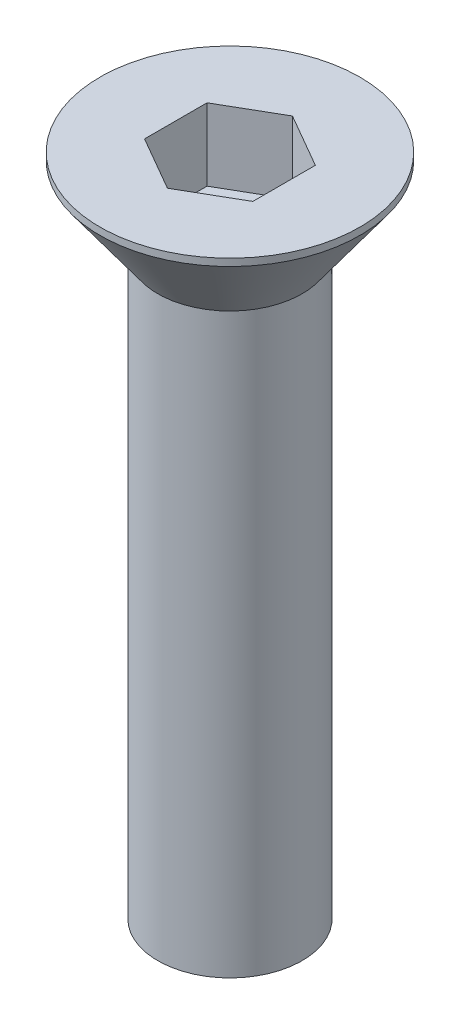
SolidWorks part; units mm, degrees
ref_plane "前视基准面" through (0, 0, 0) normal (0, 0, 1) x (1, 0, 0)
ref_plane "上视基准面" through (0, 0, 0) normal (0, 1, 0) x (1, 0, 0)
ref_plane "右视基准面" through (0, 0, 0) normal (1, 0, 0) x (0, 0, -1)
sketch "草图1" plane through (0, 0, 0) normal (0, 0, 1) x (1, 0, 0)
  line L0 (-4.4256, 0) -> (0, 0) construction
  line L1 (0, 0) -> (0, 2.2273) construction
  line L2 (0, 0) -> (1.8, 0)
  line L3 (1.8, 0) -> (1.8, -0.1)
  line L4 (1.8, -0.1) -> (1, -1.2)
  line L5 (1, -1.2) -> (0, -1.2)
  line L6 (0, -1.2) -> (0, 0)
  dimension "D1" = 1.2
  dimension "D2" = 1.8
  dimension "D3" = 0.1
  dimension "D4" = 1
revolve "旋转1" add sketch "草图1" angle 360 about L1 region at (0.738, -0.5403, 0)
sketch "草图2" plane through (0, 0, 0) normal (0, 1, 0) x (1, 0, 0)
  line L1 (0, -0.866) -> (0.75, -0.433)
  line L2 (0.75, -0.433) -> (0.75, 0.433)
  line L3 (0.75, 0.433) -> (0, 0.866)
  line L4 (0, 0.866) -> (-0.75, 0.433)
  line L5 (-0.75, 0.433) -> (-0.75, -0.433)
  line L6 (-0.75, -0.433) -> (0, -0.866)
  circle A0 centre (0, 0) radius 0.75 construction
  dimension "D1" = 1.5
extrude "切除-拉伸1" cut sketch "草图2" against normal blind 1
sketch "草图3" plane through (0, -1.2, 0) normal (0, -1, 0) x (1, 0, 0)
  circle A0 centre (0, 0) radius 1
  dimension "D1" = 2
extrude "凸台-拉伸2" add sketch "草图3" along normal blind 8
